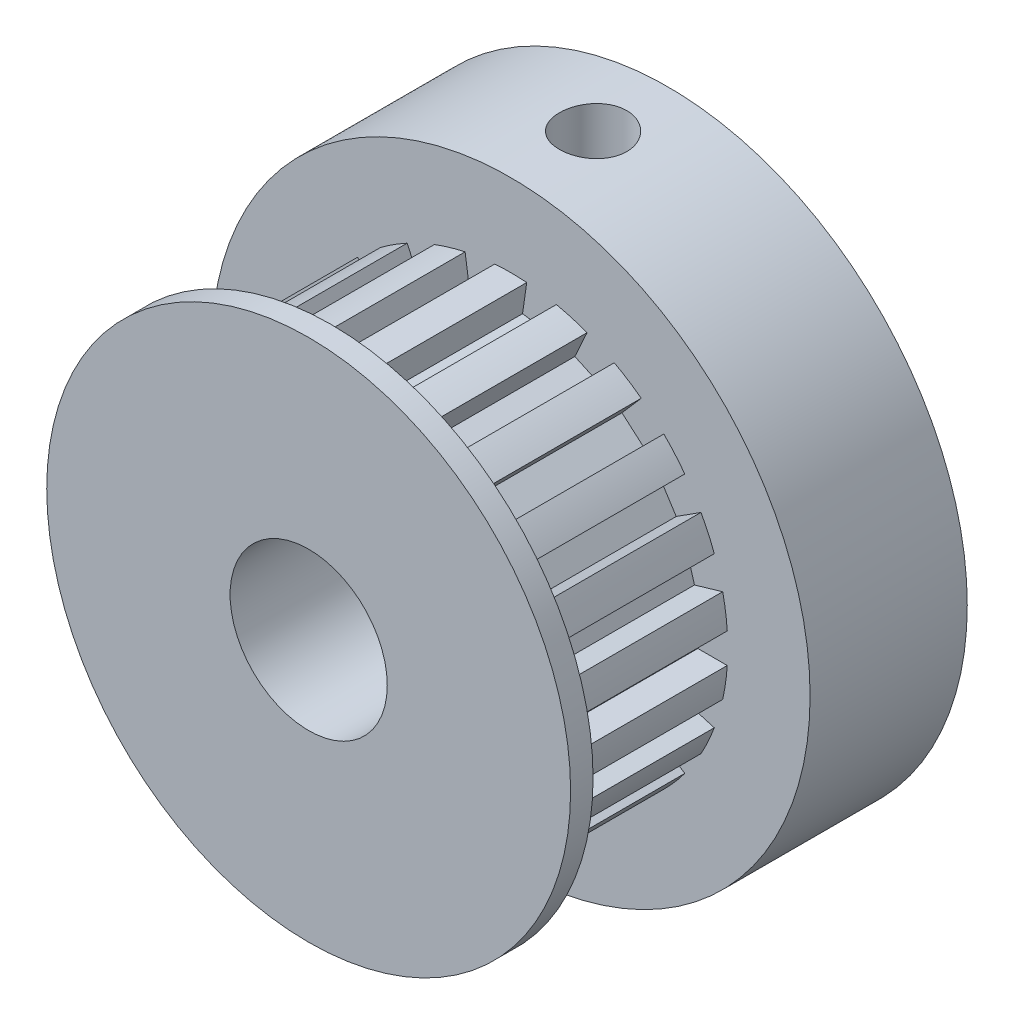
SolidWorks part; units mm, degrees
ref_plane "Front Plane" through (0, 0, 0) normal (0, 0, 1) x (1, 0, 0)
ref_plane "Top Plane" through (0, 0, 0) normal (0, 1, 0) x (1, 0, 0)
ref_plane "Right Plane" through (0, 0, 0) normal (1, 0, 0) x (0, 0, -1)
sketch "Sketch1" plane through (0, 0, 0) normal (0, 0, 1) x (1, 0, 0)
  circle A0 centre (0, 0) radius 8.89
  dimension "D1" = 17.78
extrude "Boss-Extrude1" add sketch "Sketch1" against normal blind 0.762
sketch "Sketch2" plane through (0, 0, -0.762) normal (0, 0, -1) x (-1, 0, 0)
  circle A0 centre (0, 0) radius 7.366
  dimension "D1" = 14.732
extrude "Boss-Extrude2" add sketch "Sketch2" along normal blind 6.096
sketch "Sketch3" plane through (0, 0, -6.858) normal (0, 0, -1) x (-1, 0, 0)
  circle A0 centre (0, 0) radius 10.16
  dimension "D1" = 20.32
extrude "Boss-Extrude3" add sketch "Sketch3" along normal blind 5.334
sketch "Sketch4" plane through (0, 0, 0) normal (0, 0, 1) x (1, 0, 0)
  circle A0 centre (0, 0) radius 2.667
  dimension "D1" = 5.334
extrude "Cut-Extrude1" cut sketch "Sketch4" against normal blind 25.654
ref_plane "Plane2" through (-7.366, 0, 0) normal (-1, 0, 0) x (0, 0, 1)
sketch "Sketch5" plane through (-7.366, 0, 0) normal (-1, 0, 0) x (0, 0, 1)
  line L0 (-6.858, -7.366) -> (-6.858, 7.366) construction
  line L1 (-6.858, 0.508) -> (-0.762, 0.508)
  line L2 (-6.858, 0.508) -> (-6.858, -0.508)
  line L3 (-6.858, -0.508) -> (-0.762, -0.508)
  line L4 (-0.762, 0.508) -> (-0.762, -0.508)
  line L5 (-0.762, 7.366) -> (-0.762, -7.366) construction
  point P8 (-6.858, 0)
  dimension "D1" = 1.016
extrude "Cut-Extrude2" cut sketch "Sketch5" against normal blind 1.016
ref_axis "Axis1" through (0, 0, -12.192) along (0, 0, 1)
pattern_circular "CirPattern1" count 22 over 360 about axis through (0, 0, -12.192) along (0, 0, 1) of "Cut-Extrude2"
sketch "Sketch6" plane through (0, 0, 0) normal (0, 1, 0) x (1, 0, 0)
  line L0 (10.16, 12.192) -> (-10.16, 12.192) construction
  circle A0 centre (0, 9.652) radius 1.143
  dimension "D1" = 2.286
  dimension "D2" = 2.54
extrude "Cut-Extrude3" cut sketch "Sketch6" against normal blind 22.098 and the other way blind 22.098
